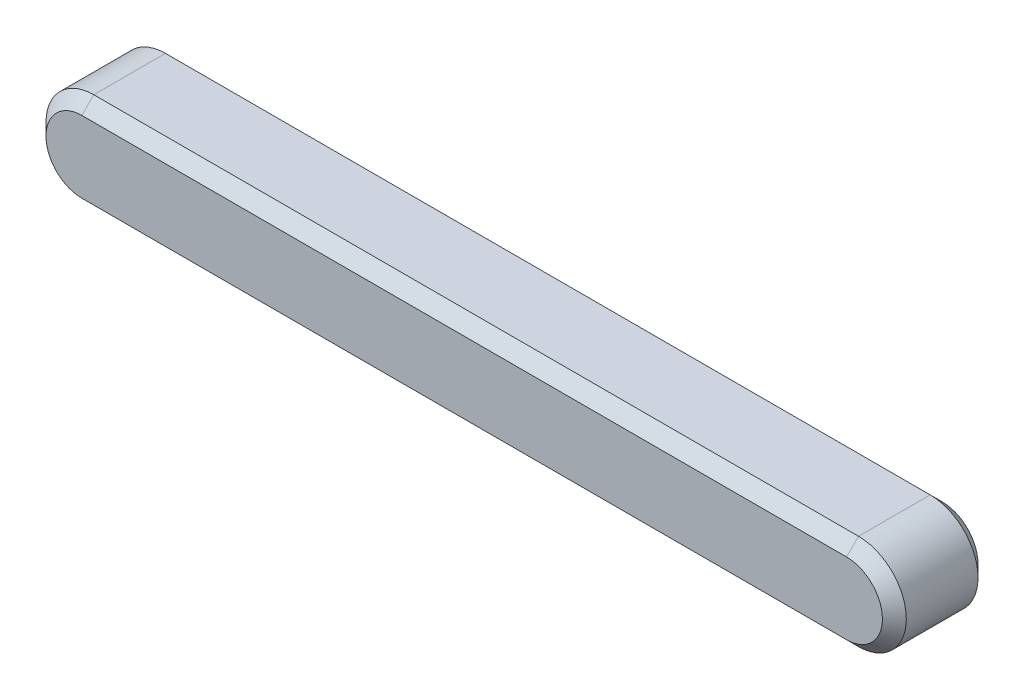
SolidWorks part; units mm, degrees
ref_plane "Front" through (0, 0, 0) normal (0, 0, 1) x (1, 0, 0)
ref_plane "Top" through (0, 0, 0) normal (0, 1, 0) x (1, 0, 0)
ref_plane "Right" through (0, 0, 0) normal (1, 0, 0) x (0, 0, -1)
sketch "body" plane through (0, 0, 0) normal (0, 0, 1) x (1, 0, 0)
  line L1 (0, 0) -> (16, 0)
  line L3 (0, 2) -> (16, 2)
  arc A0 (16, 0) -> (16, 2) centre (16, 1) ccw
  arc A1 (0, 0) -> (0, 2) centre (0, 1) cw
  dimension "Width" = 2
  dimension "Length" = 18
extrude "Extrude1" add sketch "body" along normal blind 2
chamfer "Chamfer1" distance 0.25 8 edges at (-1, 1, 0) (8, 0, 0) (17, 1, 0) (8, 2, 0) (-1, 1, 2) (8, 0, 2) (17, 1, 2) (8, 2, 2)
